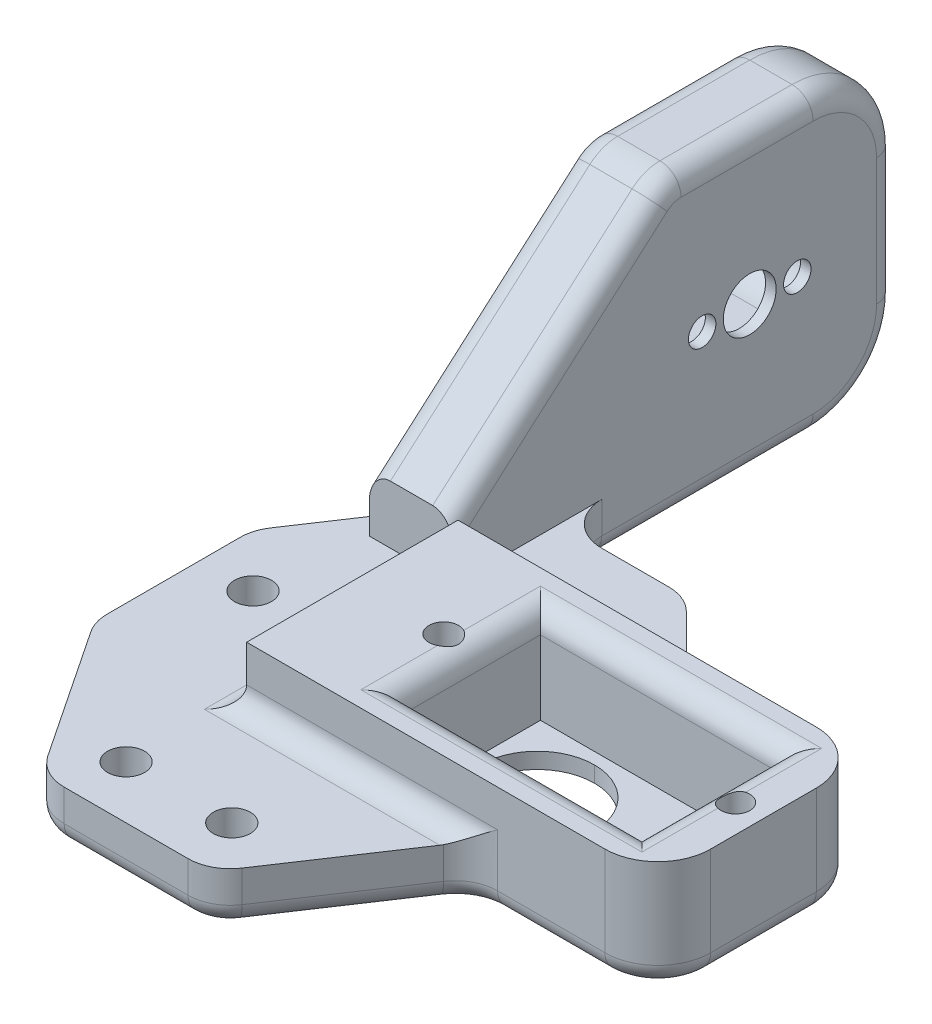
SolidWorks part; units mm, degrees
ref_plane "Front Plane" through (0, 0, 0) normal (0, 0, 1) x (1, 0, 0)
ref_plane "Top Plane" through (0, 0, 0) normal (0, 1, 0) x (1, 0, 0)
ref_plane "Right Plane" through (0, 0, 0) normal (1, 0, 0) x (0, 0, -1)
sketch "Sketch1" plane through (0, 0, 0) normal (0, 1, 0) x (1, 0, 0)
  line L0 (0, 0) -> (16.0429, 0) construction
  line L1 (16.0429, -10) -> (16.0429, 10)
  line L2 (16.0429, 10) -> (-7.9571, 10)
  line L3 (-7.9571, 10) -> (-17.9556, 19.9985)
  line L4 (-17.9556, 19.9985) -> (-33.9556, 19.9985)
  line L5 (-33.9556, 19.9985) -> (-43.9568, 4.9966)
  line L6 (-43.9568, 4.9966) -> (-43.9568, -10.0034)
  line L7 (-43.9568, -10.0034) -> (-33.9556, -25.0053)
  line L8 (-33.9556, -25.0053) -> (-17.9556, -25.0053)
  line L10 (-17.9556, -25.0053) -> (-7.9521, -10)
  line L11 (-7.9521, -10) -> (16.0429, -10)
  point P5 (16.0429, 0)
  dimension "D1" = 20
  dimension "D2" = 24
  dimension "D3" = 14.14
  dimension "D4" = 225
  dimension "D5" = 16
  dimension "D6" = 18.03
  dimension "D7" = 15
  dimension "D8" = 146.31
  dimension "D9" = 18.03
  dimension "D10" = 16
  dimension "D11" = 123.69
  dimension "D12" = 123.69
extrude "Boss-Extrude1" add sketch "Sketch1" along normal blind 5
sketch "Sketch2" plane through (0, 5, 0) normal (0, 1, 0) x (1, 0, 0)
  line L0 (16.0429, 0) -> (-57.2309, 0) construction
  line L1 (16.0429, -10) -> (16.0429, 10) construction
  line L2 (-43.9568, 4.9966) -> (-43.9568, -10.0034) construction
  line L3 (-43.9568, -10.0034) -> (-7.9521, -10) construction
  line L4 (-25.9545, -10.0017) -> (-25.9545, -20.0053) construction
  line L5 (-20.9545, -20.0053) -> (-30.9545, -20.0053) construction
  line L6 (-33.9556, -25.0053) -> (-17.9556, -25.0053) construction
  line L7 (16.0429, -10) -> (16.0429, 10) construction
  line L8 (-17.4571, 5.4) -> (-6.6571, 5.4)
  line L9 (-17.4571, 5.4) -> (-17.4571, -5.4)
  line L10 (-17.4571, -5.4) -> (-6.6571, -5.4)
  line L11 (-6.6571, 5.4) -> (-6.6571, -5.4)
  line L12 (-17.4571, 5.4) -> (-6.6571, -5.4) construction
  line L13 (-17.4571, -5.4) -> (-6.6571, 5.4) construction
  circle A0 centre (-38.9568, 0) radius 1.75
  circle A1 centre (-30.9545, -20.0053) radius 1.75
  circle A2 centre (-20.9545, -20.0053) radius 1.75
  point P18 (-25.9545, -20.0053)
  point P22 (-12.0571, 0)
  dimension "D2" = 3.5
  dimension "D5" = 3.5
  dimension "D1" = 5
  dimension "D3" = 10
  dimension "D4" = 5
  dimension "D6" = 22.7
  dimension "D7" = 10.8
  dimension "D8" = 10.8
extrude "Cut-Extrude1" cut sketch "Sketch2" against normal through all
fillet "Fillet1" 2 edges at (-17.4571, 2.5, -5.4) (-17.4571, 2.5, 5.4) type full round first side face at (-12.0571, 2.5, -5.4) second side face at (-12.0571, 2.5, 5.4) middle face at (-17.4571, 2.5, 0)
fillet "Fillet2" 2 edges at (-6.6571, 2.5, -5.4) (-6.6571, 2.5, 5.4) type full round first side face at (-9.3571, 2.5, -5.4) second side face at (-9.3571, 2.5, 5.4) middle face at (-6.6571, 2.5, 0)
fillet "Fillet3" 2 edges at (16.0429, 2.5, -10) (16.0429, 2.5, 10) type full round first side face at (4.0429, 2.5, -10) second side face at (4.0454, 2.5, 10) middle face at (16.0429, 2.5, 0)
sketch "Sketch4" plane through (0, 5, 0) normal (0, 1, 0) x (1, 0, 0)
  line L0 (-17.4571, 0) -> (-6.6571, 0) construction
  line L1 (-7.9521, -10) -> (6.0429, -10) construction
  line L2 (-23.5571, -6.5) -> (-0.5571, -6.5)
  line L3 (-23.5571, -6.5) -> (-23.5571, 6.5)
  line L4 (-23.5571, 6.5) -> (-0.5571, 6.5)
  line L5 (-0.5571, -6.5) -> (-0.5571, 6.5)
  line L6 (-23.5571, -6.5) -> (-0.5571, 6.5) construction
  line L7 (-23.5571, 6.5) -> (-0.5571, -6.5) construction
  line L8 (-29.5571, 10) -> (5.4429, 10)
  line L9 (-29.5571, 10) -> (-29.5571, -10)
  line L10 (-29.5571, -10) -> (5.4429, -10)
  line L11 (5.4429, 10) -> (5.4429, -10)
  line L12 (-29.5571, 10) -> (5.4429, -10) construction
  line L13 (-29.5571, -10) -> (5.4429, 10) construction
  arc A0 (-12.0571, 5.4) -> (-12.0571, -5.4) centre (-12.0571, 0) ccw construction
  arc A1 (-12.0571, -5.4) -> (-12.0571, 5.4) centre (-12.0571, 0) ccw construction
  point P8 (-12.0571, 0)
  point P13 (-12.0571, 0)
  dimension "D1" = 6
  dimension "D2" = 13
  dimension "D3" = 23
extrude "Boss-Extrude2" add sketch "Sketch4" along normal blind 5.5
sketch "Sketch6" plane through (0, 5, 0) normal (0, 1, 0) x (1, 0, 0)
  line L4 (-23.5571, -6.5) -> (-0.5571, -6.5)
  line L5 (-0.5571, -6.5) -> (-0.5571, 6.5)
  line L6 (-0.5571, 6.5) -> (-23.5571, 6.5)
  line L7 (-23.5571, 6.5) -> (-23.5571, -6.5)
  line L8 (-23.5571, -6.5) -> (-0.5571, -6.5)
  line L9 (-0.5571, -6.5) -> (-0.5571, 6.5)
  line L10 (-0.5571, 6.5) -> (-23.5571, 6.5)
  line L11 (-23.5571, 6.5) -> (-23.5571, -6.5)
  dimension "D1" = 0
extrude "Cut-Extrude2" cut sketch "Sketch6" against normal blind 3.5
sketch "Sketch7" plane through (0, 5, 0) normal (0, 1, 0) x (1, 0, 0)
  line L3 (5.4429, 10) -> (5.4429, -10)
  line L4 (5.4429, -10) -> (6.0429, -10)
  line L5 (6.0429, 10) -> (5.4429, 10)
  line L6 (5.4429, 10) -> (5.4429, -10)
  line L7 (5.4429, -10) -> (6.0429, -10)
  line L8 (6.0429, 10) -> (5.4429, 10)
  arc A1 (6.0429, -10) -> (6.0429, 10) centre (6.0429, 0) ccw
  arc A2 (6.0429, -10) -> (6.0429, 10) centre (6.0429, 0) ccw
  dimension "D1" = 0
extrude "Cut-Extrude3" cut sketch "Sketch7" against normal through all body kept at (-7.9521, 0, 10)
fillet "Fillet4" radius 4 2 edges at (5.4429, 5.25, 10) (5.4429, 5.25, -10)
sketch "Sketch8" plane through (0, 0, -19.9985) normal (0, 0, -1) x (-1, 0, 0)
  line L0 (17.9556, 0) -> (33.9556, 0) construction
  line L1 (29.9556, 0) -> (37.9556, 0)
  line L2 (29.9556, 0) -> (29.9556, 28)
  line L3 (29.9556, 28) -> (37.9556, 28)
  line L4 (37.9556, 0) -> (37.9556, 28)
  line L5 (33.9556, 5) -> (33.9556, 0) construction
  dimension "D1" = 4
  dimension "D2" = 4
  dimension "D3" = 28
extrude "Boss-Extrude3" add sketch "Sketch8" along normal blind 32
sketch "Sketch9" plane through (-29.9556, 0, 0) normal (1, 0, 0) x (0, 0, -1)
  line L0 (51.9985, 0) -> (19.9985, 0) construction
  line L1 (51.9985, 28) -> (51.9985, 0) construction
  line L2 (33.4985, 14) -> (42.4985, 14) construction
  circle A0 centre (37.9985, 14) radius 2.5
  circle A1 centre (33.4985, 14) radius 1.3
  circle A2 centre (42.4985, 14) radius 1.3
  point P9 (37.9985, 14)
  dimension "D1" = 5
  dimension "D5" = 2.6
  dimension "D2" = 14
  dimension "D3" = 14
  dimension "D4" = 9
extrude "Cut-Extrude4" cut sketch "Sketch9" against normal through all
fillet "Fillet5" radius 8 2 edges at (-33.9556, 0, -51.9985) (-33.9556, 28, -51.9985)
sketch "Sketch11" plane through (-29.9556, 0, 0) normal (1, 0, 0) x (0, 0, -1)
  line L0 (10, 10.5) -> (19.9985, 28)
  line L1 (19.9985, 28) -> (19.9985, 0)
  line L2 (19.9985, 0) -> (10, 0)
  line L3 (10, 0) -> (10, 10.5)
extrude "Boss-Extrude7" add sketch "Sketch11" against normal up to surface (8 mm away) up to face at (-37.9556, 14, -43.7985)
sketch "Sketch12" plane through (-37.9556, 0, 0) normal (-1, 0, 0) x (0, 0, 1)
  line L0 (-40.4985, 14) -> (-35.4985, 14) construction
  line L2 (-44.9985, 17.5) -> (-30.9985, 17.5)
  line L3 (-44.9985, 17.5) -> (-44.9985, 10.5)
  line L4 (-44.9985, 10.5) -> (-30.9985, 10.5)
  line L5 (-30.9985, 17.5) -> (-30.9985, 10.5)
  line L6 (-44.9985, 17.5) -> (-30.9985, 10.5) construction
  line L7 (-44.9985, 10.5) -> (-30.9985, 17.5) construction
  circle A0 centre (-37.9985, 14) radius 2.5 construction
  point P5 (-37.9985, 14)
  dimension "D1" = 7
  dimension "D2" = 14
extrude "Cut-Extrude5" cut sketch "Sketch12" against normal blind 7
fillet "Fillet8" 2 edges at (-34.4556, 17.5, -44.9985) (-34.4556, 10.5, -44.9985) type full round first side face at (-34.4556, 17.5, -37.9985) second side face at (-34.4556, 10.5, -37.9985) middle face at (-34.4556, 14, -44.9985)
fillet "Fillet9" 2 edges at (-34.4556, 17.5, -30.9985) (-34.4556, 10.5, -30.9985) type full round first side face at (-34.4556, 17.5, -36.2485) second side face at (-34.4556, 10.5, -36.2485) middle face at (-34.4556, 14, -30.9985)
sketch "Sketch14" plane through (-37.9556, 0, 0) normal (-1, 0, 0) x (0, 0, 1)
  line L0 (-10, 10.5) -> (-29.9985, 28)
  line L1 (-43.9985, 28) -> (-19.9985, 28) construction
  line L2 (-29.9985, 28) -> (-19.9985, 28)
  line L3 (-19.9985, 28) -> (-10, 10.5)
  dimension "D1" = 10
extrude "Cut-Extrude6" cut sketch "Sketch14" against normal through all
fillet "Fillet10" radius 4 10 edges at (-29.9556, 2.5, -19.9985) (-17.9556, 2.5, -19.9985) (-7.9571, 2.5, -10) (-7.9521, 2.5, 10) (-17.9556, 2.5, 25.0053) (-33.9556, 2.5, 25.0053) (-43.9568, 2.5, 10.0034) (-43.9568, 2.5, -4.9966) (-37.9556, 2.5, -13.9985) (-33.9556, 28, -29.9985)
sketch "Sketch16" plane through (0, 1.5, 0) normal (0, 1, 0) x (1, 0, 0)
  line L0 (-23.5571, -6.5) -> (-0.5571, -6.5) construction
  line L1 (-23.5571, 6.5) -> (-18.2571, 6.5)
  line L2 (-23.5571, 6.5) -> (-23.5571, -6.5)
  line L3 (-23.5571, -6.5) -> (-18.2571, -6.5)
  line L4 (-18.2571, 6.5) -> (-18.2571, -6.5)
  line L5 (-23.5571, 0) -> (-18.2571, 0) construction
  circle A0 centre (-20.9071, 0) radius 1.4
  dimension "D2" = 2.8
  dimension "D1" = 5.3
extrude "Boss-Extrude8" add sketch "Sketch16" along normal up to surface (9 mm away) up to face at (-7.281, 10.5, 0)
sketch "Sketch17" plane through (0, 10.5, 0) normal (0, 1, 0) x (1, 0, 0)
  line L0 (1.4429, 10) -> (9.3429, 10)
  line L1 (1.4429, -10) -> (9.3429, -10)
  line L2 (9.3429, -10) -> (9.3429, 10)
  line L3 (5.4429, -6) -> (5.4429, 6) construction
  line L4 (5.4429, -6) -> (5.4429, 6)
  arc A0 (1.4429, -10) -> (5.4429, -6) centre (1.4429, -6) ccw construction
  arc A1 (5.4429, 6) -> (1.4429, 10) centre (1.4429, 6) ccw construction
  arc A2 (1.4429, -10) -> (5.4429, -6) centre (1.4429, -6) ccw
  arc A3 (5.4429, 6) -> (1.4429, 10) centre (1.4429, 6) ccw
  dimension "D1" = 7.9
extrude "Boss-Extrude9" add sketch "Sketch17" against normal up to surface (10.5 mm away) up to face at (-22.1365, 0, -3.7768)
sketch "Sketch18" plane through (0, 10.5, 0) normal (0, 1, 0) x (1, 0, 0)
  line L0 (-20.9071, 0) -> (6.6929, 0) construction
  circle A0 centre (6.6929, 0) radius 1.35
  dimension "D2" = 2.7
  dimension "D1" = 27.6
extrude "Cut-Extrude7" cut sketch "Sketch18" against normal up to surface (9 mm away) up to face at (-20.9071, 1.5, 1.4)
fillet "Fillet11" radius 5 2 edges at (9.3429, 5.25, 10) (9.3429, 5.25, -10)
sketch "Sketch19" plane through (0, 10.5, 0) normal (0, 1, 0) x (1, 0, 0)
  line L0 (-18.2571, -6.5) -> (-0.5571, -6.5) construction
  line L1 (-0.5571, 6.5) -> (4.3429, 6.5)
  line L2 (-0.5571, 6.5) -> (-0.5571, -6.5)
  line L3 (-0.5571, -6.5) -> (4.3429, -6.5)
  line L4 (4.3429, 6.5) -> (4.3429, -6.5)
  dimension "D1" = 4.9
extrude "Cut-Extrude8" cut sketch "Sketch19" against normal up to surface (9 mm away) up to face at (-12.0571, 1.5, 0)
fillet "Fillet12" radius 2 35 edges at (-29.9556, 18.7551, -19.4337) (-29.9556, 27.7444, -30.0945) (-29.9556, 28, -37.75) (-29.9556, 25.6569, -49.6553) (-29.9556, 14, -51.9985) (-29.9556, 2.3431, -49.6553) (-29.9556, 0, -33.9985) (-28.784, 0, -21.1701) (-22.784, 0, -19.9985) (-18.0817, 0, -19.694) (-12.9563, 0, -14.9992) (-7.831, 0, -10.3045) (-0.9787, 0, -10) (-37.9556, 18.7551, -19.4337) (-37.9556, 27.7444, -30.0945) (-37.9556, 28, -37.75) (-37.9556, 25.6569, -49.6553) (-37.9556, 14, -51.9985) (-37.9556, 2.3431, -49.6553) (-37.9556, 0, -29.604) (-38.1272, 0, -14.0504) (-40.9562, 0, -9.4975) (-43.7852, 0, -4.9446) (-43.9568, 0, 2.5034) (-43.7852, 0, 9.9514) (-39.214, 0, 17.1176) (-33.7023, 0, 24.532) (-25.9556, 0, 25.0053) (-18.2089, 0, 24.532) (-12.9538, 0, 17.5026) (-7.6988, 0, 10.4733) (-0.7342, 0, 10) (7.8784, 0, 8.5355) (9.3429, 0, 0) (7.8784, 0, -8.5355)
fillet "Fillet13" radius 2 7 edges at (-17.6842, 5, 10) (-29.5571, 5, 0) (-17.9287, 5, -10) (4.3429, 10.5, 0) (-6.9571, 10.5, 6.5) (-18.2571, 10.5, 0) (-6.9571, 10.5, -6.5)
